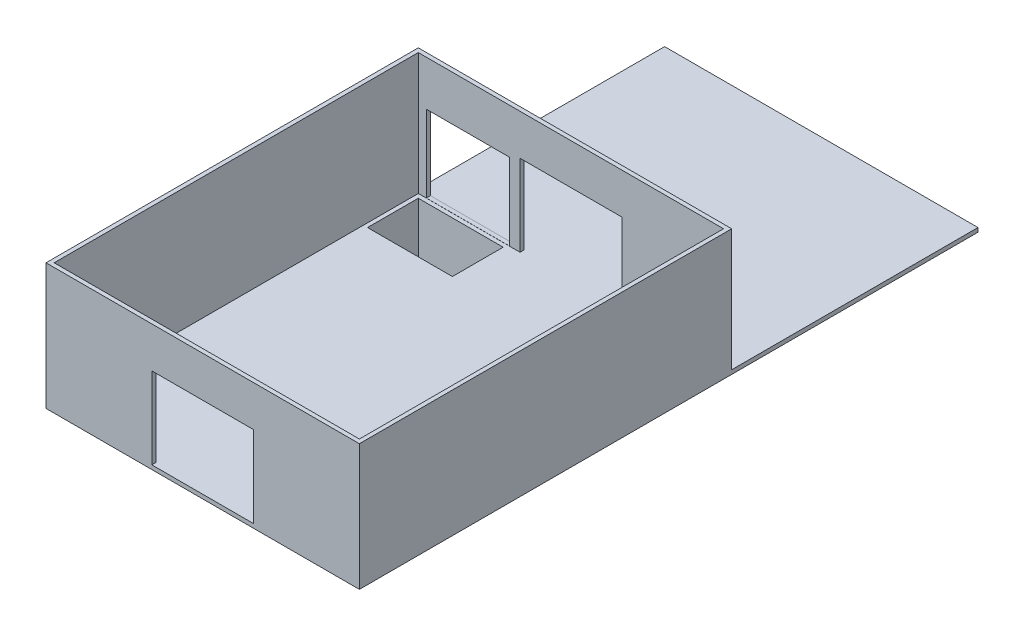
SolidWorks part; units mm, degrees
ref_plane "Alzado" through (0, 0, 0) normal (0, 0, 1) x (1, 0, 0)
ref_plane "Planta" through (0, 0, 0) normal (0, 1, 0) x (1, 0, 0)
ref_plane "Vista lateral" through (0, 0, 0) normal (1, 0, 0) x (0, 0, -1)
sketch "Croquis2" plane through (0, 0, 0) normal (0, 1, 0) x (1, 0, 0)
  line L0 (-7700, -15200) -> (7700, -15200)
  line L1 (-7500, 15000) -> (7500, 15000)
  line L2 (-7500, 15000) -> (-7500, -15000)
  line L3 (-7500, -15000) -> (7500, -15000)
  line L4 (7500, 15000) -> (7500, -15000)
  line L5 (-7500, 15000) -> (7500, -15000) construction
  line L6 (-7500, -15000) -> (7500, 15000) construction
  line L7 (7700, 15200) -> (7700, -15200)
  line L8 (-7700, 15200) -> (7700, 15200)
  line L9 (-7700, 15200) -> (-7700, -15200)
  line L11 (-7500, 3095.4256) -> (7500, 3095.4256)
  line L12 (-7500, 3095.4256) -> (-7500, 2895.4256)
  line L13 (-7500, 2895.4256) -> (7500, 2895.4256)
  line L14 (7500, 3095.4256) -> (7500, 2895.4256)
  point P0 (0, 0)
  dimension "D1" = 30000
  dimension "D2" = 15000
  dimension "D4" = 200
  dimension "D3" = 200
extrude "Saliente-Extruir1" add sketch "Croquis2" along normal blind 6000 contours L8 L9 L0 L7 L1 L4 L3 L2 | L2 L13 L4 L11 region at (-7665.9219, 0, 0) region at (0, 0, -2995.4256)
extrude "Saliente-Extruir2" add sketch "Croquis2<2>" against normal blind 200 contours L2 L11 L4 L1 | L8 L9 L0 L7 L1 L4 L3 L2 | L13 L2 L3 L4 | L2 L13 L4 L11 region at (-7665.9219, 0, 0) region at (0, 0, -9047.7128) region at (0, 0, -2995.4256) region at (0, 0, 6052.2872)
sketch "Croquis2<2>" plane through (0, 0, 0) normal (0, 1, 0) x (1, 0, 0) same geometry as "Croquis2"
sketch "Croquis5" plane through (0, 0, 15200) normal (0, 0, 1) x (1, 0, 0)
  line L0 (-7700, 0) -> (7700, 0) construction
  line L1 (-2500, 0) -> (2500, 0)
  line L2 (-2500, 0) -> (-2500, 4000)
  line L3 (-2500, 4000) -> (2500, 4000)
  line L4 (2500, 0) -> (2500, 4000)
  point P9 (0, 4000)
  dimension "D1" = 5000
extrude "Cortar-Extruir1" cut sketch "Croquis5" against normal through all
sketch "Croquis6" plane through (0, 0, 0) normal (0, 1, 0) x (1, 0, 0)
  line L0 (-7300, 2695.4256) -> (-7300, 200)
  line L1 (-7500, 2895.4256) -> (-2929.8061, 2895.4256)
  line L2 (-7500, 2895.4256) -> (-7500, 0)
  line L3 (-7500, 0) -> (-2929.8061, 0)
  line L4 (-2929.8061, 2895.4256) -> (-2929.8061, 0)
  line L5 (-7300, 200) -> (-3129.8061, 200)
  line L6 (-3129.8061, 2695.4256) -> (-3129.8061, 200)
  line L7 (-7300, 2695.4256) -> (-3129.8061, 2695.4256)
  line M21 (-2500, 2895.4256) -> (-7500, 2895.4256)
  line M22 (-7500, 2895.4256) -> (-7500, -15000)
  dimension "D1" = 200
extrude "Cortar-Extruir2" cut sketch "Croquis6" against normal through all contours L4 L3 L0 L7 L6 L5 M21 M22 | L0 L5 L6 L7 region at (-5214.903, 0, -2841.3237)
extrude "Saliente-Extruir3" add sketch "Croquis6<3>" against normal blind 2831 contours L4 L3 L0 L7 L6 L5 M21 M22 region at (-5214.903, 0, -2841.3237)
sketch "Croquis6<3>" plane through (0, 0, 0) normal (0, 1, 0) x (1, 0, 0) same geometry as "Croquis6"
extrude "Saliente-Extruir4" add sketch "Croquis6<5>" against normal blind 200 from surface contours L1 L4 L3 L2 starting at face at (-5214.903, -2831, -1447.7128)
sketch "Croquis6<5>" plane through (0, 0, 0) normal (0, 1, 0) x (1, 0, 0) same geometry as "Croquis6"
sketch "Croquis7" plane through (0, 0, -2895.4256) normal (0, 0, 1) x (1, 0, 0)
  line L1 (-3013.0885, 5.9123) -> (-7108.1343, 5.9123)
  line L2 (-3013.0885, 5.9123) -> (-3013.0885, 3786.8205)
  line L3 (-3013.0885, 3786.8205) -> (-7108.1343, 3786.8205)
  line L4 (-7108.1343, 5.9123) -> (-7108.1343, 3786.8205)
extrude "Cortar-Extruir3" cut sketch "Croquis7" against normal blind 562
sketch "Croquis8" plane through (0, 0, 0) normal (0, 1, 0) x (1, 0, 0)
  line L0 (-7500, 3095.4256) -> (7500, 3095.4256) construction
  line L1 (-11393.9987, 3095.4256) -> (13926.4264, 3095.4256)
  line L2 (-11393.9987, 3095.4256) -> (-11393.9987, 17670.1648)
  line L3 (-11393.9987, 17670.1648) -> (13926.4264, 17670.1648)
  line L4 (13926.4264, 3095.4256) -> (13926.4264, 17670.1648)
extrude "Cortar-Extruir4" cut sketch "Croquis8" along normal blind 19500
